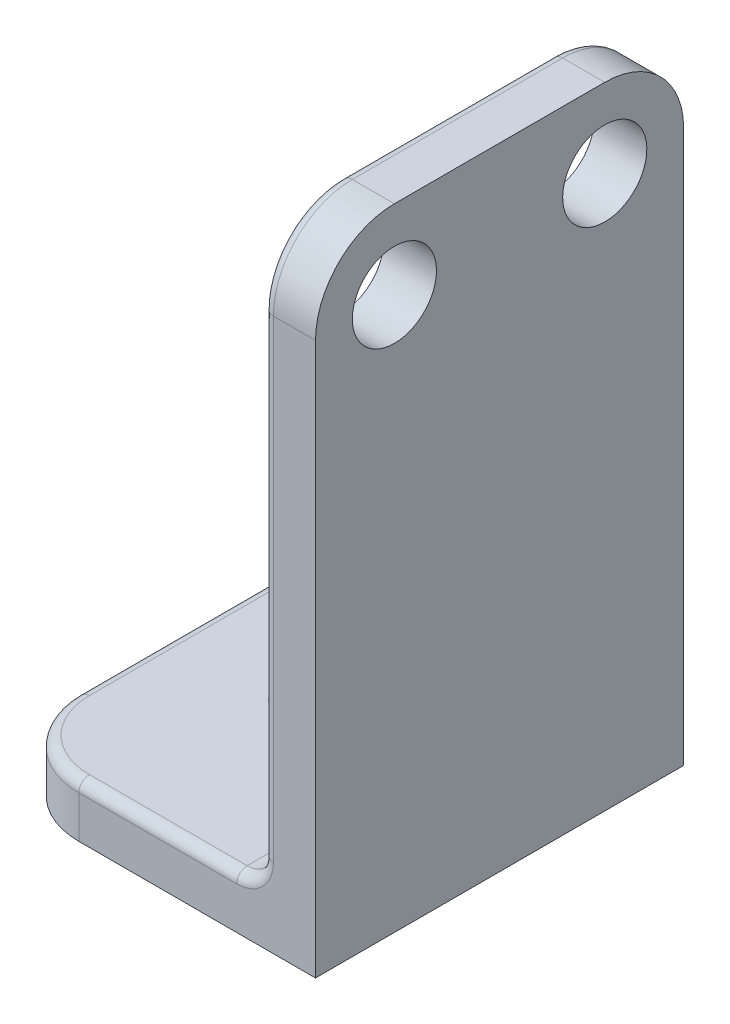
SolidWorks part; units mm, degrees
material "Простая углеродистая сталь"
ref_plane "Спереди" through (0, 0, 0) normal (0, 0, 1) x (1, 0, 0)
ref_plane "Сверху" through (0, 0, 0) normal (0, 1, 0) x (1, 0, 0)
ref_plane "Справа" through (0, 0, 0) normal (1, 0, 0) x (0, 0, -1)
sketch "Эскиз1" plane through (0, 0, 0) normal (0, 0, 1) x (1, 0, 0)
  line L0 (-10, 120) -> (-10, 10)
  line L1 (-10, 10) -> (-60, 10)
  line L2 (0, 120) -> (0, 0)
  line L3 (0, 0) -> (-60, 0)
  line L4 (-10, 120) -> (0, 120)
  line L5 (-60, 10) -> (-60, 0)
  dimension "D1" = 120
  dimension "D2" = 10
  dimension "D3" = 60
extrude "Бобышка-Вытянуть1" add sketch "Эскиз1" along normal mid plane 70
fillet "Скругление1" radius 15 4 edges at (-5, 120, 35) (-5, 120, -35) (-60, 5, -35) (-60, 5, 35)
fillet "Скругление2" radius 5 1 edges at (-10, 10, 0)
sketch "Эскиз2" plane through (0, 0, 0) normal (0, 0, 1) x (1, 0, 0)
  line L0 (-10, 10) -> (-10, 90)
  line L1 (-10, 90) -> (-40, 10)
  line L2 (-40, 10) -> (-10, 10)
  line L5 (-15, 10) -> (-45, 10) construction
  line L6 (-10, 105) -> (-10, 15) construction
  dimension "D1" = 80
  dimension "D2" = 30
extrude "Бобышка-Вытянуть2" add sketch "Эскиз2" along normal mid plane 6
fillet "Скругление3" radius 2 2 edges at (-25, 50, -3) (-25, 50, 3)
fillet "Скругление4" radius 2 24 edges at (-11.4645, 11.4645, -35) (-30, 10, -35) (-55.6066, 10, -30.6066) (-60, 10, 0) (-55.6066, 10, 30.6066) (-30, 10, 35) (-11.4645, 11.4645, 35) (-11.4645, 11.4645, 3) (-26.432, 10, 3) (-39.3744, 10, 2.4142) (-40, 10, 0) (-39.3744, 10, -2.4142) (-26.432, 10, -3) (-11.4645, 11.4645, -3) (-10, 88.3317, -2.4142) (-10, 49.652, -3) (-10, 60, -35) (-10, 115.6066, -30.6066) (-10, 120, 0) (-10, 115.6066, 30.6066) (-10, 60, 35) (-10, 49.652, 3) (-10, 88.3317, 2.4142) (-10, 90, 0)
sketch "Эскиз3" plane through (-10, 0, 0) normal (-1, 0, 0) x (0, 1, 0)
  line L0 (0, 0) -> (79.3236, 0) construction
  arc A2 (105, -33) -> (118, -20) centre (105, -20) ccw construction
  circle A3 centre (105, 20) radius 8
  circle A4 centre (105, -20) radius 8
  dimension "D1" = 16
extrude "Вырез-Вытянуть1" cut sketch "Эскиз3" against normal through all
